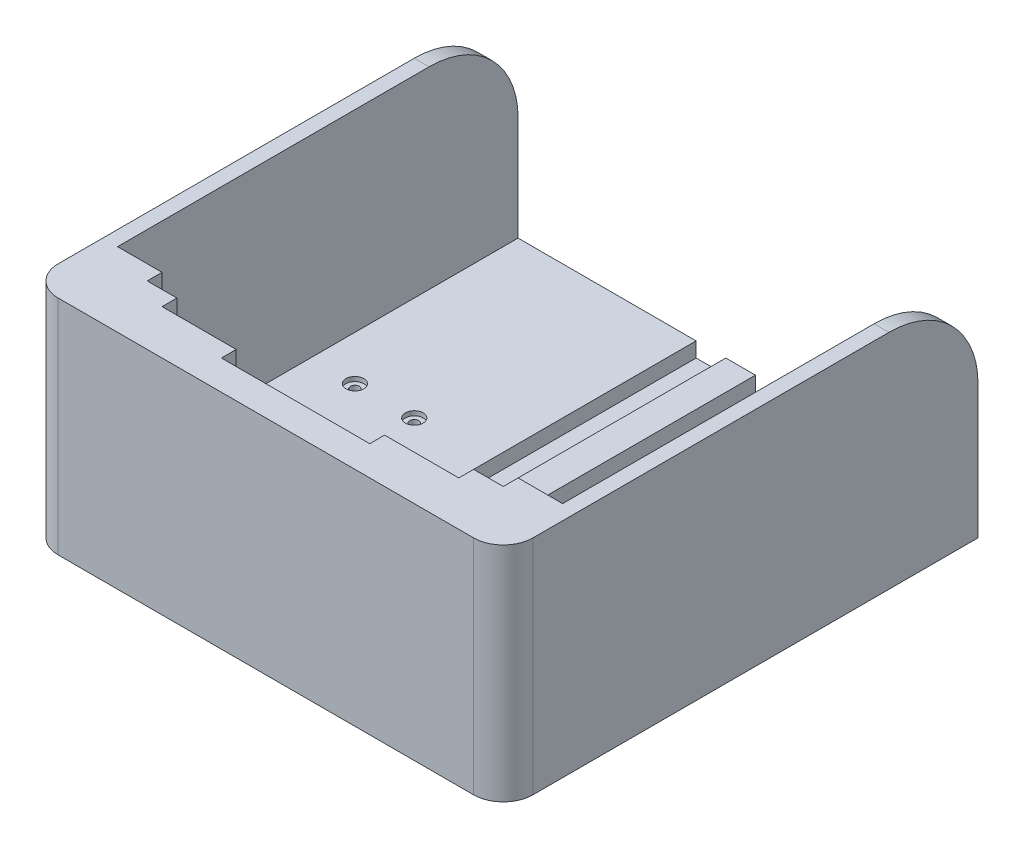
SolidWorks part; units mm, degrees
ref_plane "Front Plane" through (0, 0, 0) normal (0, 0, 1) x (1, 0, 0)
ref_plane "Top Plane" through (0, 0, 0) normal (0, 1, 0) x (1, 0, 0)
ref_plane "Right Plane" through (0, 0, 0) normal (1, 0, 0) x (0, 0, -1)
sketch "Sketch1" plane through (0, 0, 0) normal (0, 1, 0) x (1, 0, 0)
  line L1 (-80, 80) -> (80, 80)
  line L2 (-80, 80) -> (-80, -80)
  line L3 (-80, -80) -> (80, -80)
  line L4 (80, 80) -> (80, -80)
  line L5 (-80, 80) -> (80, -80) construction
  line L6 (-80, -80) -> (80, 80) construction
  point P0 (0, 0)
  dimension "D1" = 160
  dimension "D2" = 160
extrude "Boss-Extrude1" add sketch "Sketch1" along normal blind 75
sketch "Sketch2" plane through (0, 75, 0) normal (0, 1, 0) x (1, 0, 0)
  line L0 (-80, 80) -> (-80, -80) construction
  line L2 (-75, 80) -> (75, 80)
  line L4 (-75, 80) -> (-75, -70)
  line L5 (-75, -70) -> (75, -70)
  line L6 (75, 80) -> (75, -70)
  line L7 (80, -80) -> (80, 80) construction
  line L8 (80, 80) -> (-80, 80) construction
  line L9 (-80, -80) -> (80, -80) construction
  point P6 (0, 0)
  point P13 (0, 0)
  dimension "D1" = 5
  dimension "D2" = 5
  dimension "D3" = 0
  dimension "D4" = 10
extrude "Cut-Extrude1" cut sketch "Sketch2" against normal offset from surface (65 mm away) 10 up to face at (0, 0, 0)
sketch "Sketch3" plane through (0, 0, 70) normal (0, 0, -1) x (-1, 0, 0)
  line L0 (-75, 10) -> (75, 10) construction
  line L1 (-75, 75) -> (-60, 75)
  line L2 (-75, 75) -> (-75, 10)
  line L3 (-75, 10) -> (-60, 10)
  line L4 (-60, 75) -> (-60, 10)
  line L5 (0, 75) -> (0, 10) construction
  line L6 (75, 75) -> (-75, 75) construction
  line L7 (75, 10) -> (60, 10)
  line L8 (60, 75) -> (60, 10)
  line L9 (75, 75) -> (60, 75)
  line L10 (75, 75) -> (75, 10)
  dimension "D1" = 15
extrude "Boss-Extrude2" add sketch "Sketch3" along normal blind 15
sketch "Sketch4" plane through (0, 0, 70) normal (0, 0, -1) x (-1, 0, 0)
  line L0 (0, 75) -> (0, 10) construction
  line L1 (60, 75) -> (-60, 75) construction
  line L2 (75, 10) -> (-75, 10) construction
  line L3 (-60, 10) -> (60, 10) construction
  line L4 (-60, 75) -> (-50, 75)
  line L5 (-60, 75) -> (-60, 10)
  line L6 (-60, 10) -> (-50, 10)
  line L7 (-50, 75) -> (-50, 10)
  line L8 (60, 10) -> (50, 10)
  line L9 (50, 75) -> (50, 10)
  line L10 (60, 75) -> (50, 75)
  line L11 (60, 75) -> (60, 10)
  dimension "D1" = 10
extrude "Boss-Extrude3" add sketch "Sketch4" along normal blind 10
fillet "Fillet1" radius 10 2 edges at (80, 37.5, 80) (-80, 37.5, 80)
sketch "Sketch11" plane through (0, 0, 70) normal (0, 0, -1) x (-1, 0, 0)
  line L0 (-50, 10) -> (50, 10) construction
  line L1 (-50, 75) -> (-25, 75)
  line L2 (-50, 75) -> (-50, 10)
  line L3 (-50, 10) -> (-25, 10)
  line L4 (-25, 75) -> (-25, 10)
  line L5 (0, 75) -> (0, 10) construction
  line L6 (50, 75) -> (-50, 75) construction
  line L7 (75, 10) -> (-75, 10) construction
  line L8 (50, 10) -> (25, 10)
  line L9 (25, 75) -> (25, 10)
  line L10 (50, 75) -> (25, 75)
  line L11 (50, 75) -> (50, 10)
  dimension "D1" = 25
extrude "Boss-Extrude4" add sketch "Sketch11" along normal blind 5
fillet "Fillet2" radius 30 2 edges at (-77.5, 75, -80) (77.5, 75, -80)
sketch "Sketch15" plane through (0, 0, 0) normal (0, -1, 0) x (1, 0, 0)
  line L0 (-80, 0) -> (80, 0) construction
  line L1 (80, 70) -> (80, -80) construction
  line L2 (0, 0) -> (0, 80) construction
  line L3 (-70, 80) -> (70, 80) construction
  line L4 (-80, -80) -> (-80, 70) construction
  circle A0 centre (-60, 10) radius 1.5
  circle A1 centre (-40, 10) radius 1.5
  circle A2 centre (40, 10) radius 1.5
  circle A3 centre (60, 10) radius 1.5
  circle A4 centre (60, -10) radius 1.5
  circle A5 centre (40, -10) radius 1.5
  circle A6 centre (-40, -10) radius 1.5
  circle A7 centre (-60, -10) radius 1.5
  point P6 (0, 0)
  dimension "D1" = 3
  dimension "D2" = 3
  dimension "D3" = 20
  dimension "D4" = 10
  dimension "D5" = 20
extrude "Cut-Extrude2" cut sketch "Sketch15" against normal up to surface (10 mm away) up to face at (0, 10, 43.75)
sketch "Sketch17" plane through (0, 10, 0) normal (0, 1, 0) x (1, 0, 0)
  line L0 (-60, 10) -> (-40, 10) construction
  line L1 (-40, 10) -> (-40, -10) construction
  line L2 (-50, 10) -> (-50, -10) construction
  line L3 (-40, 0) -> (-59.8059, 0) construction
  line L4 (0, 24.5779) -> (0, -24.5779) construction
  circle A1 centre (-60, 10) radius 3
  circle A2 centre (-40, 10) radius 3
  circle A3 centre (-40, -10) radius 3
  circle A4 centre (-60, -10) radius 3
  circle A5 centre (40, -10) radius 3
  circle A6 centre (60, -10) radius 3
  circle A7 centre (40, 10) radius 3
  circle A8 centre (60, 10) radius 3
  point P19 (0, 0)
  dimension "D1" = 6
extrude "Cut-Extrude3" cut sketch "Sketch17" against normal blind 1.5
sketch "Sketch18" plane through (0, 10, 0) normal (0, 1, 0) x (1, 0, 0)
  line L0 (0, 80) -> (0, -70) construction
  line L1 (-75, 80) -> (75, 80) construction
  line L2 (25, -70) -> (-25, -70) construction
  line L3 (-25, -70) -> (25, -70) construction
  line L4 (5, 80) -> (15, 80)
  line L5 (5, 80) -> (5, -65)
  line L6 (5, -65) -> (15, -65)
  line L7 (15, 80) -> (15, -65)
  line L8 (-5, -65) -> (-15, -65)
  line L9 (-15, 80) -> (-15, -65)
  line L10 (-5, 80) -> (-15, 80)
  line L11 (-5, 80) -> (-5, -65)
  dimension "D1" = 10
  dimension "D2" = 0
  dimension "D3" = 10
  dimension "D4" = 5
extrude "Cut-Extrude6" cut sketch "Sketch18" against normal blind 5
